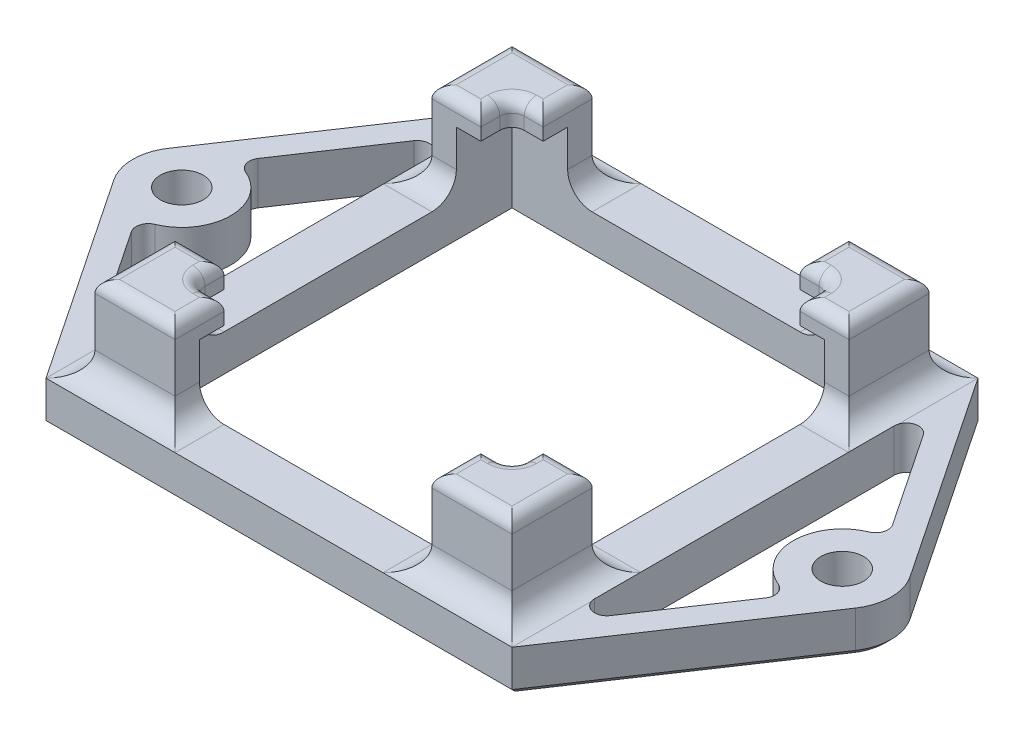
SolidWorks part; units mm, degrees
material "ABS"
ref_plane "Front Plane" through (0, 0, 0) normal (0, 0, 1) x (1, 0, 0)
ref_plane "Top Plane" through (0, 0, 0) normal (0, 1, 0) x (1, 0, 0)
ref_plane "Right Plane" through (0, 0, 0) normal (1, 0, 0) x (0, 0, -1)
sketch "Sketch1" plane through (0, 0, 0) normal (0, 1, 0) x (1, 0, 0)
  line L0 (0, 0) -> (0, 16.0612) construction
  line L2 (-15.05, -15.05) -> (15.05, -15.05)
  line L3 (-15.05, -15.05) -> (-15.05, 15.05)
  line L4 (-15.05, 15.05) -> (15.05, 15.05)
  line L5 (15.05, -15.05) -> (15.05, 15.05)
  line L6 (-15.05, -15.05) -> (15.05, 15.05) construction
  line L7 (-15.05, 15.05) -> (15.05, -15.05) construction
  line L8 (-19.05, 19.05) -> (19.05, 19.05)
  line L10 (-19.05, -19.05) -> (19.05, -19.05)
  line L11 (30.323, -2.2266) -> (19.05, -19.05)
  line L12 (30.323, 2.2266) -> (19.05, 19.05)
  line L13 (-30.323, -2.2266) -> (-19.05, -19.05)
  line L14 (-30.323, 2.2266) -> (-19.05, 19.05)
  line L16 (-19.05, -19.05) -> (-19.05, 19.05) construction
  line L17 (19.05, -19.05) -> (19.05, 19.05) construction
  circle A0 centre (-27, 0) radius 1.75
  circle A1 centre (27, 0) radius 1.75
  arc A2 (-30.323, 2.2266) -> (-30.323, -2.2266) centre (-27, 0) ccw
  arc A3 (30.323, -2.2266) -> (30.323, 2.2266) centre (27, 0) ccw
  point P10 (0, 0)
  dimension "D2" = 3.5
  dimension "D5" = 8
  dimension "D1" = 54
  dimension "D3" = 30.1
  dimension "D4" = 4
extrude "Boss-Extrude1" add sketch "Sketch1" along normal blind 3.5
sketch "Sketch2" plane through (0, 3.5, 0) normal (0, 1, 0) x (1, 0, 0)
  line L0 (-10.5, -13.05) -> (-10.5, -17.05)
  line L1 (10.5, -13.05) -> (10.5, -17.05)
  line L2 (0, -17.05) -> (0, 17.05) construction
  line L3 (-17.05, 0) -> (17.05, 0) construction
  line L4 (10.5, 17.05) -> (10.5, 13.05)
  line L5 (-10.5, 17.05) -> (-10.5, 13.05)
  line L6 (-17.05, 10.5) -> (-13.05, 10.5)
  line L7 (-17.05, -10.5) -> (-13.05, -10.5)
  line L8 (13.05, -10.5) -> (17.05, -10.5)
  line L9 (13.05, 10.5) -> (17.05, 10.5)
  line L10 (10.5, -13.05) -> (13.05, -13.05)
  line L11 (-17.05, -17.05) -> (-10.5, -17.05)
  line L12 (-17.05, -17.05) -> (-17.05, -10.5)
  line L13 (-17.05, 17.05) -> (-10.5, 17.05)
  line L14 (13.05, 13.05) -> (-13.05, 13.05)
  line L15 (13.05, -13.05) -> (13.05, 13.05)
  line L16 (-13.05, -13.05) -> (13.05, -13.05)
  line L17 (-13.05, 13.05) -> (-13.05, -13.05)
  line L18 (13.05, 13.05) -> (10.5, 13.05)
  line L19 (13.05, -13.05) -> (13.05, -10.5)
  line L20 (-13.05, -13.05) -> (-10.5, -13.05)
  line L21 (-13.05, 13.05) -> (-13.05, 10.5)
  line L22 (17.05, -17.05) -> (17.05, -10.5)
  line L23 (-17.05, -17.05) -> (17.05, 17.05) construction
  line L24 (-17.05, 17.05) -> (17.05, -17.05) construction
  line L25 (10.5, -17.05) -> (17.05, -17.05)
  line L26 (10.5, 17.05) -> (17.05, 17.05)
  line L27 (-10.5, 13.05) -> (-13.05, 13.05)
  line L28 (13.05, 10.5) -> (13.05, 13.05)
  line L29 (17.05, 10.5) -> (17.05, 17.05)
  line L30 (-17.05, 10.5) -> (-17.05, 17.05)
  line L31 (-13.05, -10.5) -> (-13.05, -13.05)
  point P0 (0, 0)
  dimension "D2" = 4
  dimension "D3" = 21
  dimension "D4" = 21
  dimension "D5" = 34.1
  dimension "D6" = 34.1
  dimension "D1" = 2
extrude "Boss-Extrude2" add sketch "Sketch2" along normal blind 2 from offset 5
chamfer "Chamfer1" distance 0.5 angle 45 14 edges at (0, 0, 15.05) (-15.05, 0, 0) (0, 0, -15.05) (15.05, 0, 0) (0, 0, 19.05) (24.6865, 0, 10.6383) (31, 0, 0) (24.6865, 0, -10.6383) (0, 0, -19.05) (-24.6865, 0, -10.6383) (-31, 0, 0) (-24.6865, 0, 10.6383) (-27, 0, 1.75) (27, 0, 1.75)
sketch "Sketch3" plane through (0, 3.5, 0) normal (0, 1, 0) x (1, 0, 0)
  line L18 (-26.7332, -3.9911) -> (-19, -15.5318)
  line L19 (-19, -15.5318) -> (-19, 15.5318)
  line L20 (-19, 15.5318) -> (-26.7332, 3.9911)
  line L21 (-27, 0) -> (0, 0) construction
  line L22 (-30.323, -2.2266) -> (-19.05, -19.05) construction
  circle A9 centre (-27, 0) radius 4
  arc A10 (-30.323, 2.2266) -> (-30.323, -2.2266) centre (-27, 0) ccw construction
  dimension "D1" = 2
  dimension "D2" = 8
extrude "Cut-Extrude1" cut sketch "Sketch3" against normal through all contours L21 A9 L18 L19 | A9 L21 L19 L20 region at (-21.5561, 3.5, 6.1285) region at (-21.5561, 3.5, -6.1285)
fillet "Fillet2" radius 1 4 edges at (-19, 1.75, -15.5318) (-19, 1.75, 15.5318) (-26.7332, 1.75, -3.9911) (-26.7332, 1.75, 3.9911)
mirror "Mirror1" about plane through (0, 0, 0) normal (1, 0, 0) of "Fillet2", "Cut-Extrude1"
sketch "Sketch4" plane through (0, 3.5, 0) normal (0, 1, 0) x (1, 0, 0)
  line L0 (-15.05, -15.05) -> (-15.05, 0)
  line L1 (-17.05, -17.05) -> (-10.5, -17.05)
  line L2 (-17.05, -17.05) -> (-17.05, -10.5)
  line L3 (-17.05, 17.05) -> (-10.5, 17.05)
  line L4 (17.05, -17.05) -> (17.05, -10.5)
  line L5 (-17.05, -17.05) -> (17.05, 17.05) construction
  line L6 (-17.05, 17.05) -> (17.05, -17.05) construction
  line L7 (-15.05, 15.05) -> (-10.5, 15.05)
  line L8 (15.05, -15.05) -> (15.05, -10.5)
  line L9 (-15.05, -15.05) -> (-10.5, -15.05)
  line L10 (17.05, 10.5) -> (15.05, 10.5)
  line L11 (15.05, -10.5) -> (17.05, -10.5)
  line L12 (10.5, -15.05) -> (10.5, -17.05)
  line L13 (-10.5, -15.05) -> (-10.5, -17.05)
  line L14 (0, -17.05) -> (0, 17.05) construction
  line L15 (17.05, 0) -> (-17.05, 0) construction
  line L16 (-17.05, 10.5) -> (-15.05, 10.5)
  line L17 (-15.05, -10.5) -> (-17.05, -10.5)
  line L18 (-10.5, 17.05) -> (-10.5, 15.05)
  line L19 (10.5, 17.05) -> (10.5, 15.05)
  line L20 (15.05, 10.5) -> (15.05, 15.05)
  line L21 (17.05, 10.5) -> (17.05, 17.05)
  line L22 (15.05, -15.05) -> (15.05, 15.05) construction
  line L23 (-15.05, 10.5) -> (-15.05, 15.05)
  line L24 (17.05, -17.05) -> (17.05, 17.05) construction
  line L25 (-17.05, 10.5) -> (-17.05, 17.05)
  line L26 (-15.05, -15.05) -> (-15.05, 15.05) construction
  line L27 (10.5, -17.05) -> (17.05, -17.05)
  line L28 (-17.05, -17.05) -> (-17.05, 17.05) construction
  line L29 (10.5, -15.05) -> (15.05, -15.05)
  line L30 (-17.05, -17.05) -> (17.05, -17.05) construction
  line L31 (10.5, 15.05) -> (15.05, 15.05)
  line L32 (-15.05, -15.05) -> (15.05, -15.05) construction
  line L33 (10.5, 17.05) -> (17.05, 17.05)
  line L34 (-15.05, 15.05) -> (15.05, 15.05) construction
  line L36 (-17.05, 17.05) -> (17.05, 17.05) construction
  point P0 (0, 0)
  line M42 (-15.05, 15.05) -> (15.05, 15.05)
  line M43 (15.05, 15.05) -> (15.05, -15.05)
  line M44 (15.05, -15.05) -> (-15.05, -15.05)
  line M45 (-15.05, -15.05) -> (-15.05, 15.05)
  dimension "D1" = 34.1
  dimension "D3" = 21
  dimension "D4" = 21
  dimension "D5" = 34.1
  dimension "D2" = 2
extrude "Boss-Extrude3" add sketch "Sketch4" along normal up to surface (5 mm away) contours L17 L2 L1 L13 M45 M44 | L25 L16 L18 L3 M45 M42 | L33 L19 L10 L21 M42 M43 | L12 L27 L4 L11 M43 M44 region at (-12.775, 3.5, 15.1426) region at (12.775, 3.5, 15.1426) region at (-16.05, 3.5, -10.5926) region at (15.1426, 3.5, -12.775) up to face at (-13.5333, 8.5, 13.5333)
fillet "Fillet3" radius 2 16 edges at (-10.5, 3.5, -16.05) (10.5, 3.5, -16.05) (16.05, 3.5, -10.5) (16.05, 3.5, 10.5) (10.5, 3.5, 16.05) (-10.5, 3.5, 16.05) (-16.05, 3.5, 10.5) (-16.05, 3.5, -10.5) (-17.05, 3.5, -13.775) (-13.775, 3.5, -17.05) (13.775, 3.5, -17.05) (17.05, 3.5, -13.775) (17.05, 3.5, 13.775) (13.775, 3.5, 17.05) (-17.05, 3.5, 13.775) (-13.775, 3.5, 17.05)
fillet "Fillet4" radius 1 28 edges at (15.05, 10.5, -10.5) (13.05, 10.5, -11.775) (11.775, 10.5, -13.05) (10.5, 10.5, -15.05) (13.775, 10.5, -17.05) (17.05, 10.5, -13.775) (10.5, 10.5, 15.05) (11.775, 10.5, 13.05) (13.05, 10.5, 11.775) (15.05, 10.5, 10.5) (17.05, 10.5, 13.775) (13.775, 10.5, 17.05) (-15.05, 10.5, 10.5) (-13.05, 10.5, 11.775) (-11.775, 10.5, 13.05) (-10.5, 10.5, 15.05) (-13.775, 10.5, 17.05) (-17.05, 10.5, 13.775) (-13.775, 10.5, -17.05) (-10.5, 10.5, -15.05) (-11.775, 10.5, -13.05) (-13.05, 10.5, -11.775) (-15.05, 10.5, -10.5) (-17.05, 10.5, -13.775) (13.05, 9.5, -13.05) (13.05, 9.5, 13.05) (-13.05, 9.5, 13.05) (-13.05, 9.5, -13.05)
